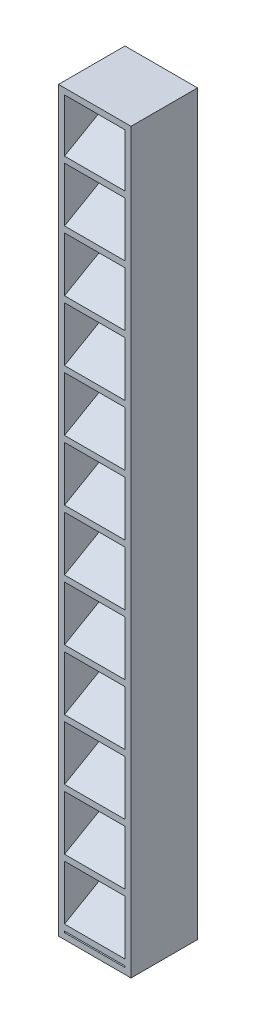
SolidWorks part; units mm, degrees
ref_plane "Plano frontal" through (0, 0, 0) normal (0, 0, 1) x (1, 0, 0)
ref_plane "Plano superior" through (0, 0, 0) normal (0, 1, 0) x (1, 0, 0)
ref_plane "Plano direito" through (0, 0, 0) normal (1, 0, 0) x (0, 0, -1)
sketch "Esboço1" plane through (0, 0, 0) normal (0, 0, 1) x (1, 0, 0)
  line L1 (-6, -61) -> (6, -61)
  line L2 (-6, -61) -> (-6, 61)
  line L3 (-6, 61) -> (6, 61)
  line L4 (6, -61) -> (6, 61)
  line L5 (-6, -61) -> (6, 61) construction
  line L6 (-6, 61) -> (6, -61) construction
  point P0 (0, 0)
  dimension "D1" = 122
  dimension "D2" = 12
extrude "Ressalto-extrusão1" add sketch "Esboço1" along normal blind 1
sketch "Esboço2" plane through (0, 0, 1) normal (0, 0, 1) x (1, 0, 0)
  line L1 (-5, -60) -> (5, -60)
  line L2 (-5, -60) -> (-5, 60)
  line L3 (-5, 60) -> (5, 60)
  line L4 (5, -60) -> (5, 60)
  line L5 (-5, -60) -> (5, 60) construction
  line L6 (-5, 60) -> (5, -60) construction
  line L7 (-6, -61) -> (6, -61)
  line L8 (-6, -61) -> (-6, 61)
  line L9 (-6, 61) -> (6, 61)
  line L10 (6, -61) -> (6, 61)
  line L11 (-6, -61) -> (6, 61) construction
  line L12 (-6, 61) -> (6, -61) construction
  point P0 (0, 0)
  point P6 (0, 0)
  dimension "D1" = 120
  dimension "D2" = 10
  dimension "D3" = 122
  dimension "D4" = 12
extrude "Ressalto-extrusão2" add sketch "Esboço2" along normal blind 10
sketch "Esboço3" plane through (0, 0, 1) normal (0, 0, 1) x (1, 0, 0)
  line L0 (-5, 60) -> (-5, -60) construction
  line L1 (-5, 57) -> (5, 57)
  line L2 (-5, 57) -> (-5, 56)
  line L3 (-5, 56) -> (5, 56)
  line L4 (5, 57) -> (5, 56)
  line L5 (5, -60) -> (5, 60) construction
  line L6 (5, 60) -> (-5, 60) construction
  dimension "D1" = 3
  dimension "D2" = 1
sketch "Esboço4" plane through (-5, 0, 0) normal (1, 0, 0) x (0, 0, -1)
  line L0 (-1, 56) -> (-11, 50.2265)
  line L1 (-11, 60) -> (-11, -60) construction
  line L2 (-1, 60) -> (-1, -60) construction
  dimension "D1" = 60
extrude "Ressalto-extrusão3" add sketch "Esboço3" along direction (0, -0.5, 0.866) on the side of the normal up to surface (10 mm away) contours L3 L4 L1 L2 up to face at (0, 0, 11)
pattern_linear "Padrão linear1" count 12 spacing 10 along (0, -1, 0) of "Ressalto-extrusão3"
